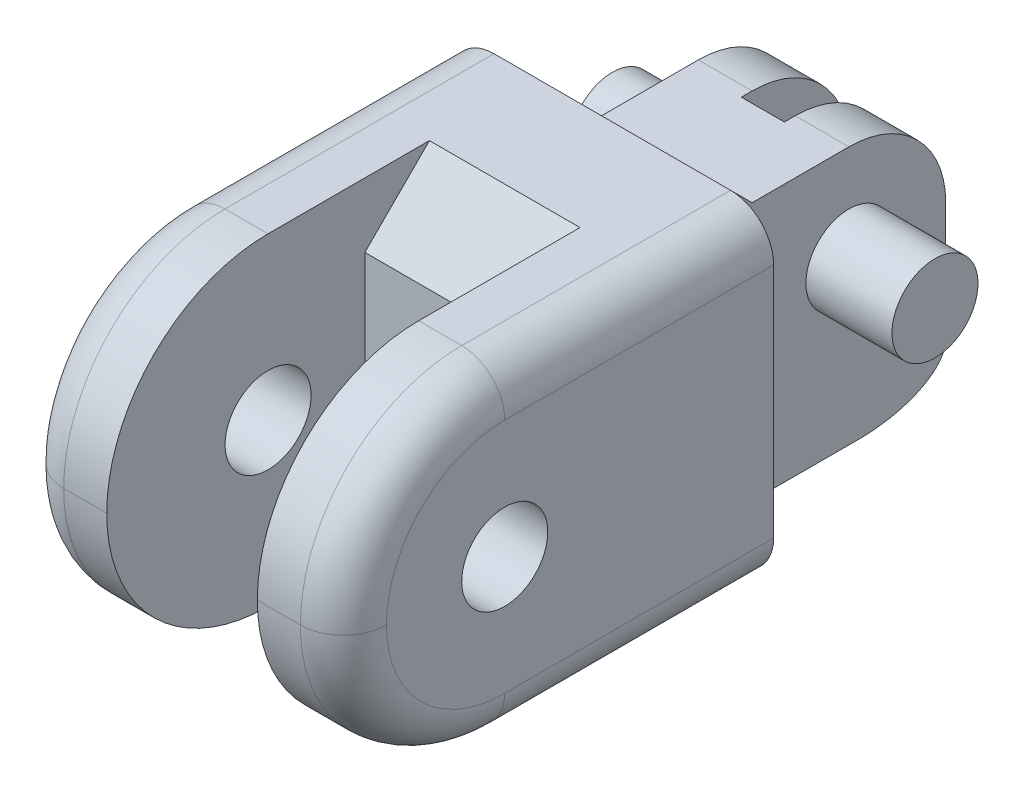
SolidWorks part; units mm, degrees
ref_plane "Front Plane" through (0, 0, 0) normal (0, 0, 1) x (1, 0, 0)
ref_plane "Top Plane" through (0, 0, 0) normal (0, 1, 0) x (1, 0, 0)
ref_plane "Right Plane" through (0, 0, 0) normal (1, 0, 0) x (0, 0, -1)
sketch "Sketch1" plane through (0, 0, 0) normal (0, 0, 1) x (1, 0, 0)
  line L1 (-7.5, 7.5) -> (7.5, 7.5)
  line L2 (-7.5, 7.5) -> (-7.5, -7.5)
  line L3 (-7.5, -7.5) -> (7.5, -7.5)
  line L4 (7.5, 7.5) -> (7.5, -7.5)
  line L5 (-7.5, 7.5) -> (7.5, -7.5) construction
  line L6 (-7.5, -7.5) -> (7.5, 7.5) construction
  point P0 (0, 0)
  dimension "D1" = 15
  dimension "D2" = 15
extrude "Boss-Extrude1" add sketch "Sketch1" along normal blind 35 contours L2 L1 L4 L3
sketch "Sketch3" plane through (0, 0, 35) normal (0, 0, 1) x (1, 0, 0)
  line L0 (-7.5, -7.5) -> (7.5, -7.5) construction
  line L1 (-3.5, 7.5) -> (3.5, 7.5)
  line L2 (-3.5, 7.5) -> (-3.5, -7.5)
  line L3 (-3.5, -7.5) -> (3.5, -7.5)
  line L4 (3.5, 7.5) -> (3.5, -7.5)
  line L5 (-3.5, 7.5) -> (3.5, -7.5) construction
  line L6 (-3.5, -7.5) -> (3.5, 7.5) construction
  point P0 (0, 0)
  dimension "D1" = 7
extrude "Cut-Extrude1" cut sketch "Sketch3" against normal blind 12
sketch "Sketch4" plane through (7.5, 0, 0) normal (1, 0, 0) x (0, 0, -1)
  line L0 (-38.6919, 0) -> (3.3242, 0) construction
  line L1 (-35, 7.5) -> (-35, -7.5) construction
  circle A0 centre (-27.5, 0) radius 2
  dimension "D2" = 4
  dimension "D1" = 7.5
extrude "Cut-Extrude2" cut sketch "Sketch4" against normal blind 15
sketch "Sketch5" plane through (0, 0, 0) normal (0, 0, -1) x (-1, 0, 0)
  line L0 (7.5, -7.5) -> (-7.5, -7.5) construction
  line L1 (-7.5, 7.5) -> (-3.5, 7.5)
  line L2 (-7.5, 7.5) -> (-7.5, -7.5)
  line L3 (-7.5, -7.5) -> (-3.5, -7.5)
  line L4 (-3.5, 7.5) -> (-3.5, -7.5)
  line L5 (-7.5, 7.5) -> (-3.5, -7.5) construction
  line L6 (-7.5, -7.5) -> (-3.5, 7.5) construction
  line L8 (3.5, 7.5) -> (7.5, 7.5)
  line L9 (3.5, 7.5) -> (3.5, -7.5)
  line L10 (3.5, -7.5) -> (7.5, -7.5)
  line L11 (7.5, 7.5) -> (7.5, -7.5)
  line L12 (3.5, 7.5) -> (7.5, -7.5) construction
  line L13 (3.5, -7.5) -> (7.5, 7.5) construction
  point P0 (-5.5, 0)
  point P7 (5.5, 0)
  dimension "D1" = 4
  dimension "D2" = 4
  dimension "D3" = 3.5
  dimension "D4" = 3.5
extrude "Cut-Extrude3" cut sketch "Sketch5" against normal blind 15
sketch "Sketch6" plane through (0, 0, 0) normal (1, 0, 0) x (0, 0, -1)
  circle A0 centre (-7.5, 0) radius 2
  dimension "D1" = 7.5
extrude "Boss-Extrude2" add sketch "Sketch6" along normal blind 7.5 and the other way blind 7.5
fillet "Fillet1" radius 7.5 4 edges at (5.5, -7.5, 35) (-5.5, -7.5, 35) (-5.5, 7.5, 35) (5.5, 7.5, 35)
sketch "Sketch7" plane through (0, 0, 0) normal (1, 0, 0) x (0, 0, -1)
  line L0 (-39.1207, 0) -> (4.4951, 0) construction
  line L7 (0, -7.5) -> (0, 7.5) construction
  line L17 (-23, 7.5) -> (-23, 4.5)
  line L18 (-23, 4.5) -> (-20, 7.5)
  line L19 (-27.5, 7.5) -> (-15, 7.5) construction
  line L20 (-20, 7.5) -> (-23, 7.5)
  dimension "D4" = 3
  dimension "D5" = 20
extrude "Cut-Extrude6" cut sketch "Sketch7" against normal blind 3.5 and the other way blind 3.5
fillet "Fillet2" radius 2 8 edges at (-7.5, -7.5, 21.25) (-7.5, -5.3033, 32.8033) (-7.5, 5.3033, 32.8033) (7.5, -7.5, 21.25) (7.5, -5.3033, 32.8033) (7.5, 5.3033, 32.8033) (-7.5, 7.5, 21.25) (7.5, 7.5, 21.25)
sketch "Sketch8" plane through (0, 0, 0) normal (1, 0, 0) x (0, 0, -1)
  line L0 (-15, 7.5) -> (-12, 4.5)
  line L1 (-12, 4.5) -> (-7.5, 4.5)
  line L2 (-15, 7.5) -> (0, 7.5) construction
  line L3 (-7.5, 0) -> (-7.5, 14.3736) construction
  line L7 (0, -7.5) -> (0, 7.5)
  line L8 (0, 7.5) -> (-15, 7.5)
  line L9 (-3, 0) -> (-3, -7.5)
  line L10 (-15, -7.5) -> (0, -7.5) construction
  line L11 (-3, -7.5) -> (0, -7.5)
  arc A1 (-7.5, 4.5) -> (-3, 0) centre (-7.5, 0) cw
  dimension "D1" = 3
  dimension "D2" = 45
extrude "Cut-Extrude7" cut sketch "Sketch8" against normal blind 7.5 and the other way blind 7.5
fillet "Fillet3" radius 4 1 edges at (0, -7.5, 3) second distance 2 first distance on face at (0, -7.5, 18.5)
sketch "Sketch9" plane through (0, 0, 0) normal (1, 0, 0) x (0, 0, -1)
  line L0 (-13.9466, 0) -> (1.0526, 0) construction
  line L1 (-7.5, 0) -> (-7.5, 8.6585) construction
  line L2 (-8, -0.5) -> (-8, 9.1476)
  line L3 (-8, -0.5) -> (1.6476, -0.5)
  arc A0 (-8, 9.1476) -> (1.6476, -0.5) centre (-8, -0.5) cw
  dimension "D1" = 0.5
  dimension "D2" = 0.5
extrude "Cut-Extrude8" cut sketch "Sketch9" against normal blind 1 and the other way blind 1
